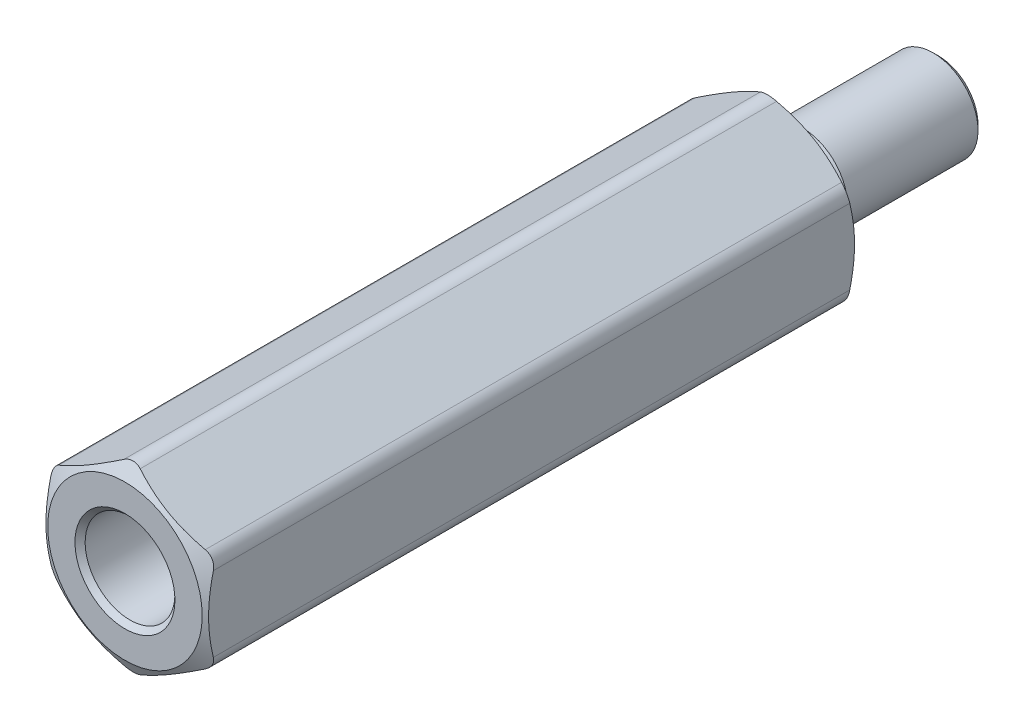
SolidWorks part; units mm, degrees
material "6061-T6 (SS)"
ref_plane "Front Plane" through (0, 0, 0) normal (0, 0, 1) x (1, 0, 0)
ref_plane "Top Plane" through (0, 0, 0) normal (0, 1, 0) x (1, 0, 0)
ref_plane "Right Plane" through (0, 0, 0) normal (1, 0, 0) x (0, 0, -1)
sketch "Sketch1" plane through (0, 0, 0) normal (0, 0, 1) x (1, 0, 0)
  line L1 (3.175, 1.8331) -> (0, 3.6662)
  line L2 (0, 3.6662) -> (-3.175, 1.8331)
  line L3 (-3.175, 1.8331) -> (-3.175, -1.8331)
  line L4 (-3.175, -1.8331) -> (0, -3.6662)
  line L5 (0, -3.6662) -> (3.175, -1.8331)
  line L6 (3.175, -1.8331) -> (3.175, 1.8331)
  circle A0 centre (0, 0) radius 3.175 construction
  point P10 (0, -3.175)
  dimension "Hex Size" = 6.35
sketch "Sketch2" plane through (0, 0, 0) normal (1, 0, 0) x (0, 0, -1)
  line L0 (6.35, 0) -> (-25.4, 0) construction
  line L2 (0, 1.7526) -> (0, -1.7526) construction
  line L3 (-15.875, 1.7526) -> (-15.875, -1.7526) construction
  line L4 (-26.1441, 1.8385) -> (-25.7473, 1.1511) construction
  line L5 (-25.7473, 1.1511) -> (-25.3504, 1.8385) construction
  line L6 (-25.3504, 1.8385) -> (-26.1441, 1.8385) construction
  line L7 (-26.0945, 1.7526) -> (-25.4, 1.7526) construction
  line L8 (-25.7969, 1.237) -> (-25.6977, 1.237) construction
  line L9 (-25.7473, 1.237) -> (-25.7473, 1.1511) construction
  line L10 (-25.7473, 1.7526) -> (-25.7473, 1.8385) construction
  line L11 (6.3004, 1.8385) -> (7.0941, 1.8385) construction
  line L12 (7.0941, 1.8385) -> (6.6973, 1.1511) construction
  line L13 (6.6973, 1.1511) -> (6.3004, 1.8385) construction
  line L14 (6.35, 1.7526) -> (7.0445, 1.7526) construction
  line L15 (6.6477, 1.237) -> (6.7469, 1.237) construction
  line L16 (6.6973, 1.237) -> (6.6973, 1.1511) construction
  line L17 (6.6973, 1.7526) -> (6.6973, 1.8385) construction
  line L18 (0, 3.6662) -> (-25.4, 3.6662) construction
  point P6 (0, 0)
  point P9 (-15.875, 0)
  dimension "Length" = 25.4
sketch "Sketch3" plane through (0, 0, 0) normal (1, 0, 0) x (0, 0, -1)
  line L0 (-15.875, 0) -> (6.35, 0)
  line L1 (-15.875, 1.7526) -> (-15.875, -1.7526) construction
  line L2 (6.35, 0) -> (6.35, 1.5542)
  line L3 (6.35, 1.5542) -> (6.1516, 1.7526)
  line L4 (6.1516, 1.7526) -> (1.0597, 1.7526)
  line L5 (1.0597, 1.7526) -> (0.762, 1.237)
  line L6 (-15.875, 0) -> (-15.875, 1.5542)
  line L7 (-15.875, 1.5542) -> (-16.0734, 1.7526)
  line L8 (-16.0734, 1.7526) -> (-25.2016, 1.7526)
  line L9 (-25.2016, 1.7526) -> (-25.4, 1.951)
  line L10 (6.1516, 0) -> (6.1516, -1.7526) construction
  line L11 (-25.4, 1.951) -> (-25.4, 3.175)
  line L12 (-25.4, 3.175) -> (0, 3.175)
  line L14 (0.762, 1.237) -> (0.1984, 1.237)
  line L15 (0, 1.4355) -> (0, 3.175)
  arc A0 (0, 1.4355) -> (0.1984, 1.237) centre (0.1984, 1.4355) ccw
  point P5 (-25.4, -3.175)
  point P8 (-23.4156, -1.7526)
  point P9 (4.3656, -1.7526)
  point P27 (0, 1.237)
  dimension "D4" = 0.1984
  dimension "D2" = 0.1984
  dimension "D1" = 45
  dimension "D6" = 1.9844
  dimension "D7" = 60
  dimension "D3" = 1.9844
  dimension "D5" = 0.762
revolve "Revolve1" add sketch "Sketch3" angle 360 about L0 region at (0, 1.6409, 8.6394)
sketch "Sketch4" plane through (0, 0, 25.4) normal (0, 0, 1) x (1, 0, 0)
  line L0 (0, 3.175) -> (0, 1.7526) construction
  line L1 (-3.175, 1.8331) -> (-3.175, -1.8331)
  line L2 (-3.175, -1.8331) -> (0, -3.6662)
  line L3 (0, -3.6662) -> (3.175, -1.8331)
  line L4 (3.175, -1.8331) -> (3.175, 1.8331)
  line L5 (3.175, 1.8331) -> (0, 3.6662)
  line L6 (0, 3.6662) -> (-3.175, 1.8331)
  circle A0 centre (0, 0) radius 3.175 construction
  circle A1 centre (0, 0) radius 2.4638
  circle A2 centre (0, 0) radius 3.175 construction
  point P16 (0, 2.4638)
extrude "Boss-Extrude1" add sketch "Sketch4" against normal up to surface (25.4 mm away) up to face at (0, 3.175, 0)
sketch "Sketch5" plane through (0, 0, 25.4) normal (0, 0, 1) x (1, 0, 0)
  line L0 (-1.0053, 1.4356) -> (1.0053, -1.4356) construction
  line L1 (0, 1.7526) -> (0, -1.7526) construction
  line L3 (0, -2.9435) -> (0, 2.9435) construction
  circle A0 centre (0, 0) radius 3.0162
  point P11 (1.0053, -1.4356)
  dimension "D1" = 6.0325
  dimension "D2" = 35
extrude "Cut-Extrude1" cut sketch "Sketch5" against normal through all draft 60 flip side to cut
sketch "Sketch6" plane through (0, 0, 0) normal (0, 0, -1) x (-1, 0, 0)
  circle A0 centre (0, 0) radius 3.0162
  circle A1 centre (0, 0) radius 3.0162 construction
extrude "Cut-Extrude2" cut sketch "Sketch6" against normal through all draft 60 flip side to cut
fillet "Fillet1" radius 0.635 6 edges at (0, 3.6662, 12.7) (-3.175, -1.8331, 12.7) (0, -3.6662, 12.7) (3.175, -1.8331, 12.7) (3.175, 1.8331, 12.7) (-3.175, 1.8331, 12.7)
sketch "Drawing1" plane through (0, 0, 0) normal (1, 0, 0) x (0, 0, -1)
  line L0 (-25.4, 1.7526) -> (-15.875, 1.7526) construction
  line L1 (-15.875, 1.7526) -> (-15.875, -1.7526) construction
  line L2 (-15.875, -1.7526) -> (-25.4, -1.7526) construction
sketch "Sketch7" [suppressed] plane through (0, 0, 0) normal (-1, 0, 0) x (0, 0, 1)
  line L0 (-6.6477, 1.237) -> (-6.7469, 1.237)
  line L1 (-6.7469, 1.237) -> (-7.0693, 1.7956)
  line L2 (-7.0941, 1.8385) -> (-6.6973, 1.1511) construction
  line L3 (-7.0693, 1.7956) -> (-6.3252, 1.7956)
  line L4 (-6.6973, 1.1511) -> (-6.3004, 1.8385) construction
  line L5 (-6.3252, 1.7956) -> (-6.6477, 1.237)
  line L6 (-6.6973, 1.7526) -> (-6.6973, 1.8385) construction
  point P12 (-6.6973, 1.7956)
sketch "Sketch8" [suppressed] plane through (0, 0, -6.35) normal (0, 0, -1) x (-1, 0, 0)
  circle A0 centre (0, 0) radius 1.7526
curve "Helix/Spiral1" [suppressed] pitch 0.7937 height 6.1595 turns 7.76
sweep "Cut-Sweep1" [suppressed] cut profiles "Sketch7" path "Helix/Spiral1"
sketch "Sketch9" [suppressed] plane through (0, 0, 15.875) normal (0, 0, 1) x (1, 0, 0)
  circle A0 centre (0, 0) radius 1.951
extrude "Boss-Extrude2" [suppressed] add sketch "Sketch9" along normal up to surface (9.525 mm away)
sketch "Sketch10" [suppressed] plane through (0, 0, 0) normal (1, 0, 0) x (0, 0, -1)
  line L0 (6.35, 0) -> (-25.4, 0) construction
  line L1 (-15.875, 1.7526) -> (-25.4, 1.7526)
  line L2 (-15.875, 1.7526) -> (-15.875, 0)
  line L3 (-15.875, 0) -> (-25.4, 0)
  line L4 (-25.4, 1.7526) -> (-25.4, 0)
revolve "Revolve2" [suppressed] add sketch "Sketch10" angle 360 about L0
sketch "Sketch11" [suppressed] plane through (0, 0, 25.4) normal (0, 0, 1) x (1, 0, 0)
  circle A0 centre (0, 0) radius 1.7526
  circle A1 centre (0, 0) radius 1.7526 construction
sketch "Sketch12" [suppressed] plane through (0, 0, 0) normal (1, 0, 0) x (0, 0, -1)
  line L0 (-25.7969, 1.237) -> (-25.6977, 1.237)
  line L1 (-25.6977, 1.237) -> (-25.3752, 1.7956)
  line L2 (-25.7473, 1.1511) -> (-25.3504, 1.8385) construction
  line L3 (-25.3752, 1.7956) -> (-26.1193, 1.7956)
  line L4 (-26.1441, 1.8385) -> (-25.7473, 1.1511) construction
  line L5 (-26.1193, 1.7956) -> (-25.7969, 1.237)
  line L6 (-25.7473, 1.7526) -> (-25.7473, 1.8385) construction
  point P12 (-25.7473, 1.7956)
curve "Helix/Spiral2" [suppressed] pitch 0.7937 height 10.3187 turns 13
sweep "Cut-Sweep2" [suppressed] cut profiles "Sketch12" path "Helix/Spiral2"
combine bodies "Combine1" [suppressed] operation type subtract main body 113 bodies to subtract 114
sketch "Sketch13" [suppressed] plane through (0, 0, 25.4) normal (0, 0, 1) x (1, 0, 0)
  circle A0 centre (0, 0) radius 1.8034
  dimension "D1" = 0.0508
extrude "Cut-Extrude3" [suppressed] cut sketch "Sketch13" against normal blind 1.1906 draft 44.759
equation "\"Thread Pitch (B)/8@Sketch2\" = \"Thread Pitch (B)@Sketch2\" / 8"
equation "\"Thread Pitch (A)/8@Sketch2\" = \"Thread Pitch (A)@Sketch2\" / 8"
equation "\"D1@Sketch5\" = \"Hex Size@Sketch1\" * .95"
equation "\"D1@Fillet1\" = \"Hex Size@Sketch1\" * .1"
equation "\"D2@Sketch3\" = \"Thread Pitch (A)@Sketch2\" * .25"
equation "\"D4@Sketch3\" = \"D2@Sketch3\""
equation "\"D6@Sketch3\" = \"Thread Pitch (A)@Sketch2\" * 2.5"
equation "\"D3@Helix/Spiral1\" = \"Thread Length (A)@Sketch2\" - \"D5@Sketch3\" * .25"
equation "\"D4@Helix/Spiral1\" = \"Thread Pitch (A)@Sketch2\""
equation "\"D3@Sketch3\" = \"Thread Pitch (B)@Sketch2\" * 2.5"
equation "\"D5@Sketch3\" = \"Thread Length (A)@Sketch2\" * .12"
equation "\"D3@Helix/Spiral2\" = \"Minimum Thread Length (B)@Sketch2\" + \"Thread Pitch (B)@Sketch2\""
equation "\"D4@Helix/Spiral2\" = \"Thread Pitch (B)@Sketch2\""
equation "\"Pitch Natural Taper Angle\"= ATN ( \"Thread Pitch (B)@Sketch2\" / 2 )"
equation "\"Angle Count\"= 45 / \"Pitch Natural Taper Angle\""
equation "\"Rounded Angle Count\"= ROUND ( \"Angle Count\" )"
equation "\"Taper Angle\"= \"Rounded Angle Count\" * \"Pitch Natural Taper Angle\""
equation "\"D1@Cut-Extrude3\"=\"Thread Pitch (B)@Sketch2\"*1.5"
equation "\"D3@Cut-Extrude3\"=\"Taper Angle\""
